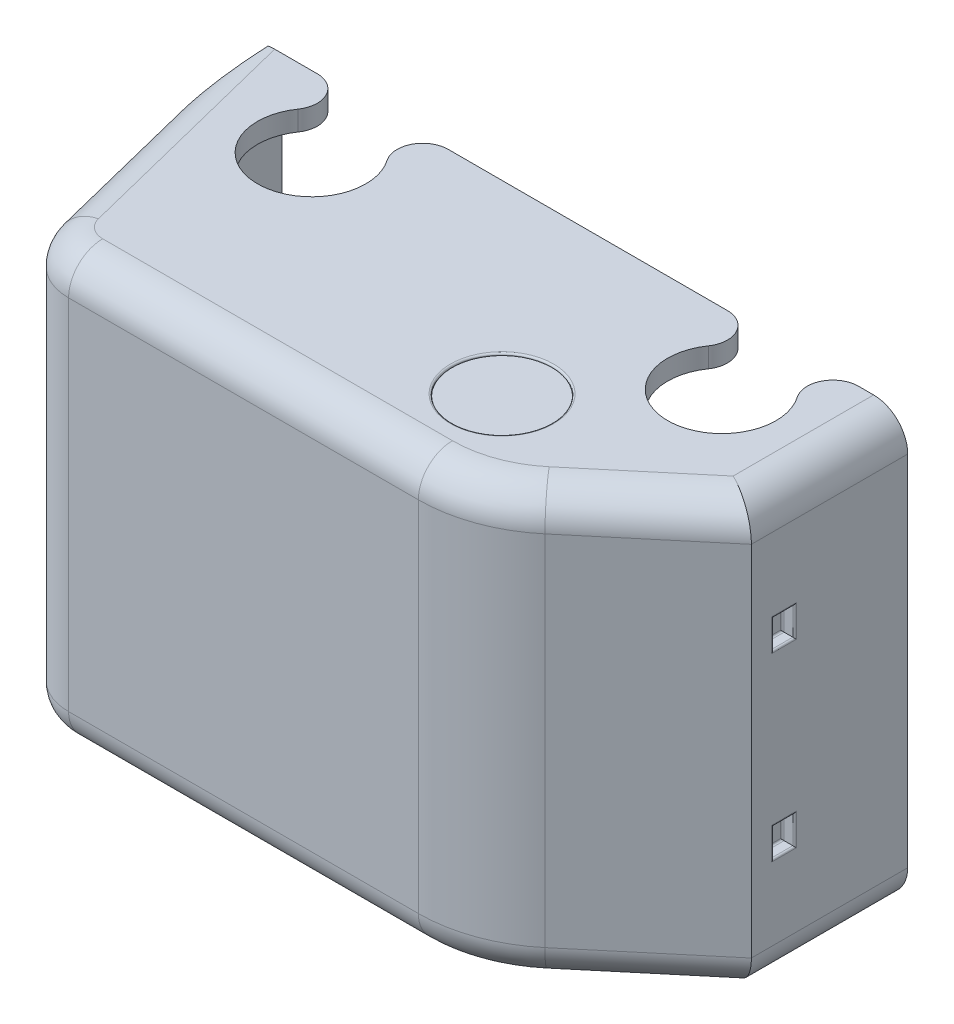
SolidWorks part; units mm, degrees
ref_plane "Front Plane" through (0, 0, 0) normal (0, 0, 1) x (1, 0, 0)
ref_plane "Top Plane" through (0, 0, 0) normal (0, 1, 0) x (1, 0, 0)
ref_plane "Right Plane" through (0, 0, 0) normal (1, 0, 0) x (0, 0, -1)
sketch "Sketch1" plane through (0, 0, 0) normal (0, 0, 1) x (1, 0, 0)
  line L1 (0, 0) -> (225, 0)
  line L2 (0, 0) -> (0, 150)
  line L3 (0, 150) -> (225, 150)
  line L4 (225, 0) -> (225, 150)
  dimension "D1" = 225
  dimension "D2" = 150
extrude "Boss-Extrude1" add sketch "Sketch1" along normal blind 70 and the other way blind 30 contours L2 L1 L4 L3
sketch "Sketch2" plane through (0, 0, 0) normal (0, -1, 0) x (1, 0, 0)
  line L0 (112.5, 70) -> (112.5, -30)
  line L1 (0, 70) -> (225, 70) construction
  line L2 (0, -30) -> (225, -30) construction
  line L3 (171.3711, 70) -> (225, 25)
  line L4 (225, 70) -> (225, -30) construction
  line L5 (225, 25) -> (225, 70)
  line L6 (225, 70) -> (171.3711, 70)
  line L7 (15, 70) -> (0, 10)
  line L8 (0, 10) -> (0, 70)
  line L9 (0, 70) -> (15, 70)
  line M8 (225, -30) -> (225, 70)
  line M9 (225, 70) -> (0, 70)
  dimension "D1" = 50
  dimension "D2" = 45
  dimension "D3" = 15
  dimension "D4" = 60
extrude "Cut-Extrude1" cut sketch "Sketch2" against normal through all contours L3 M9 M8 | L9 L7 L8 region at (207.1237, 0, 55)
sketch "Sketch8" plane through (0, 0, 0) normal (0, -1, 0) x (1, 0, 0)
  line L0 (0, -30) -> (225, -30) construction
  line L1 (112.5, -5) -> (112.5, 70) construction
  line L3 (15, 70) -> (171.3711, 70) construction
  line L4 (112.5, -5) -> (184.625, -5) construction
  line L5 (112.5, -5) -> (40.375, -5) construction
  circle A0 centre (184.625, -5) radius 19.05
  circle A1 centre (40.375, -5) radius 19.05
  arc A2 (24.7281, -15.8663) -> (17.3358, -30) centre (17.3358, -21) cw
  arc A3 (56.0219, -15.8663) -> (63.4142, -30) centre (63.4142, -21) ccw
  arc A4 (200.2719, -15.8663) -> (207.6642, -30) centre (207.6642, -21) ccw
  arc A5 (168.9781, -15.8663) -> (161.5858, -30) centre (161.5858, -21) cw
  line M6 (0, -30) -> (225, -30)
  dimension "D1" = 38.1
  dimension "D5" = 9
  dimension "D2" = 72.125
  dimension "D3" = 75
  dimension "D4" = 97.5
ref_plane "Plane2" through (0, 75, 0) normal (0, 1, 0) x (1, 0, 0)
sketch "Sketch7" plane through (0, 75, 0) normal (0, 1, 0) x (1, 0, 0)
  line L3 (225, -25) -> (225, 30) construction
  line L4 (215, 30.6155) -> (215, -26.864)
  line L6 (5, -9.3845) -> (5, 30.6155)
  line L7 (0, 30) -> (0, -10) construction
  line L9 (215, 30.6155) -> (5, 30.6155)
  line L13 (220, -22.6685) -> (169.5512, -65)
  line L14 (220, 30) -> (220, -22.6685)
  line L15 (169.5512, -65) -> (18.9039, -65)
  line L16 (18.9039, -65) -> (4.8507, -8.7873)
  line L17 (215, -26.864) -> (169.5512, -65)
  line L19 (169.5512, -65) -> (18.9039, -65)
  line L20 (18.9039, -65) -> (5, -9.3845)
  dimension "D2" = 10
  dimension "D3" = 40
  dimension "D4" = 5
  dimension "D1" = 5
extrude "Cut-Extrude2" cut sketch "Sketch7" against normal offset from surface 7 and the other way offset from surface 7 up to face at (106.0618, 0, 19.1667) other way up to face at (106.0618, 150, 19.1667)
extrude "Cut-Extrude3" cut sketch "Sketch8" against normal blind 185 contours A1 | A3 A1 A2 M6 | A0 | A0 A5 A4 M6 region at (184.625, 0, -5) region at (40.375, 0, -26.1004) region at (184.625, 0, -26.1004) region at (40.375, 0, -5)
ref_plane "Plane3" through (0, 37.5, 0) normal (0, 1, 0) x (1, 0, 0)
ref_plane "Plane4" through (0, 112.5, 0) normal (0, 1, 0) x (1, 0, 0)
ref_plane "Plane5" through (147.32, 0, 0) normal (1, 0, 0) x (0, 0, -1)
ref_plane "Plane6" through (0, 0, 35) normal (0, 0, 1) x (1, 0, 0)
sketch "Sketch9" plane through (0, 0, -30) normal (0, 0, -1) x (-1, 0, 0)
  line L1 (0, 0) -> (-17.3358, 0) construction
  line L2 (-205.7195, 0) -> (-228.4047, -0.4781)
  line L3 (-228.4047, -0.4781) -> (-228.4047, -8.991)
  line L4 (-228.4047, -8.991) -> (-264.5886, -8.991)
  line L5 (-264.5886, -8.991) -> (-264.5886, 4.8205)
  line L6 (-251.3583, 23.1181) -> (-264.5886, 4.8205)
  line L7 (-225.4605, 16.5) -> (-225, 16.5) construction
  line L9 (-225, 0) -> (-225, 150) construction
  arc A1 (-225, 16.5) -> (-205.7195, 0) centre (-206.1209, 19.0458) ccw
  arc A2 (-225, 16.5) -> (-251.3583, 23.1181) centre (-239.501, 14.5446) ccw
  point P4 (-218.5071, 4.5722)
  dimension "D2" = 19.05
ref_plane "Plane7" through (0, 0, 0) normal (0, -1, 0) x (-1, 0, 0)
sketch "Sketch12" plane through (0, 0, 0) normal (0, -1, 0) x (-1, 0, 0)
  line L4 (-171.3711, -70) -> (-225, -25) construction
  line L5 (-225.6845, -24.4256) -> (-178.9425, -63.5491)
  arc A1 (-218.5071, 30) -> (-225.6845, -24.4256) centre (-204.8147, 0.5082) ccw
fillet "Fillet1" radius 12 8 edges at (198.1855, 0, 47.5) (225, 0, -2.5) (7.5, 0, 40) (93.1855, 0, 70) (7.5, 150, 40) (93.1855, 150, 70) (198.1855, 150, 47.5) (225, 150, -2.5) tangent propagation no
fillet "Fillet2" radius 50.8 3 edges at (170.0918, 3.5147, 66.4853) (170.0918, 146.4853, 66.4853) (171.3711, 75, 70)
fillet "Fillet3" radius 19.05 3 edges at (17.7442, 3.5147, 66.4853) (17.7442, 146.4853, 66.4853) (15, 75, 70)
sketch "Sketch13" plane through (225, 0, 0) normal (1, 0, 0) x (0, 0, -1)
  line L24 (-9.8, 48.2) -> (-17.2, 48.2)
  line L25 (-17.2, 48.2) -> (-17.2, 38.3)
  line L26 (-9.8, 38.3) -> (-9.8, 48.2)
  line L27 (-17.2, 38.3) -> (-9.8, 38.3)
  line L28 (-9.8, 48.2) -> (-17.2, 48.2)
  line L29 (-17.2, 48.2) -> (-17.2, 38.3)
  line L30 (-9.8, 38.3) -> (-9.8, 48.2)
  line L31 (-17.2, 38.3) -> (-9.8, 38.3)
  dimension "D1" = 0.05
extrude "Cut-Extrude4" cut sketch "Sketch13" against normal blind 4.318
fillet "Fillet4" radius 0.635 8 edges at (220.682, 38.3, 13.5) (220.682, 43.25, 17.2) (220.682, 48.2, 13.5) (220.682, 43.25, 9.8) (225, 38.3, 13.5) (225, 43.25, 17.2) (225, 48.2, 13.5) (225, 43.25, 9.8)
mirror "Mirror2" about plane through (0, 75, 0) normal (0, 1, 0) of "Cut-Extrude4", "Fillet4"
sketch "Sketch14" plane through (0, 0, 0) normal (0, -1, 0) x (1, 0, 0)
  circle A3 centre (147.32, 35) radius 17.5254
  circle A4 centre (147.32, 35) radius 17.5254
  dimension "D1" = 0.0254
extrude "Cut-Extrude5" cut sketch "Sketch14" against normal blind 0.75 contours A4
fillet "Fillet5" radius 0.635 1 edges at (147.32, 0, 17.4746)
mirror "Mirror4" about plane through (0, 75, 0) normal (0, 1, 0) of "Cut-Extrude5"
fillet "Fillet6" radius 0.635 1 edges at (147.32, 150, 17.4746)
sketch "Sketch16" plane through (-2.3529, 0, 0.5882) normal (-0.9701, 0, 0.2425) x (0.2425, 0, 0.9701)
  line L20 (35.302, 107.45) -> (35.302, 117.55)
  line L21 (20.202, 107.45) -> (35.302, 107.45)
  line L22 (20.202, 117.55) -> (20.202, 107.45)
  line L23 (35.302, 117.55) -> (20.202, 117.55)
  line L24 (35.302, 107.45) -> (35.302, 117.55)
  line L25 (20.202, 107.45) -> (35.302, 107.45)
  line L26 (20.202, 117.55) -> (20.202, 107.45)
  line L27 (35.302, 117.55) -> (20.202, 117.55)
  dimension "D1" = 0.05
extrude "Cut-Extrude6" cut sketch "Sketch16" against normal blind 3.05 contours L24 L27 L26 L25
mirror "Mirror5" about plane through (0, 75, 0) normal (0, 1, 0) of "Cut-Extrude6"
ref_plane "Plane8" through (-2.3529, 0, 0.5882) normal (-0.9701, 0, 0.2425) x (0.2425, 0, 0.9701)
ref_plane "Plane9" through (6.7309, 0, 26.9234) normal (0.2425, 0, 0.9701) x (0.9701, 0, -0.2425)
ref_axis "Axis1" through (184.625, 200.9796, -5) along (0, -1, 0)
ref_axis "Axis2" through (40.375, 265.4765, -5) along (0, -1, 0)
fillet "Fillet7" [suppressed] radius 5
ref_plane "Plane11" through (0, 150, 0) normal (0, 1, 0) x (1, 0, 0)
equation "\"tol\"= 0.05mm"
equation "\"D1@Sketch16\"=\"tol\""
equation "\"D1@Cut-Extrude6\"=3mm+\"tol\""
equation "\"D1@Sketch13\"=\"tol\""
